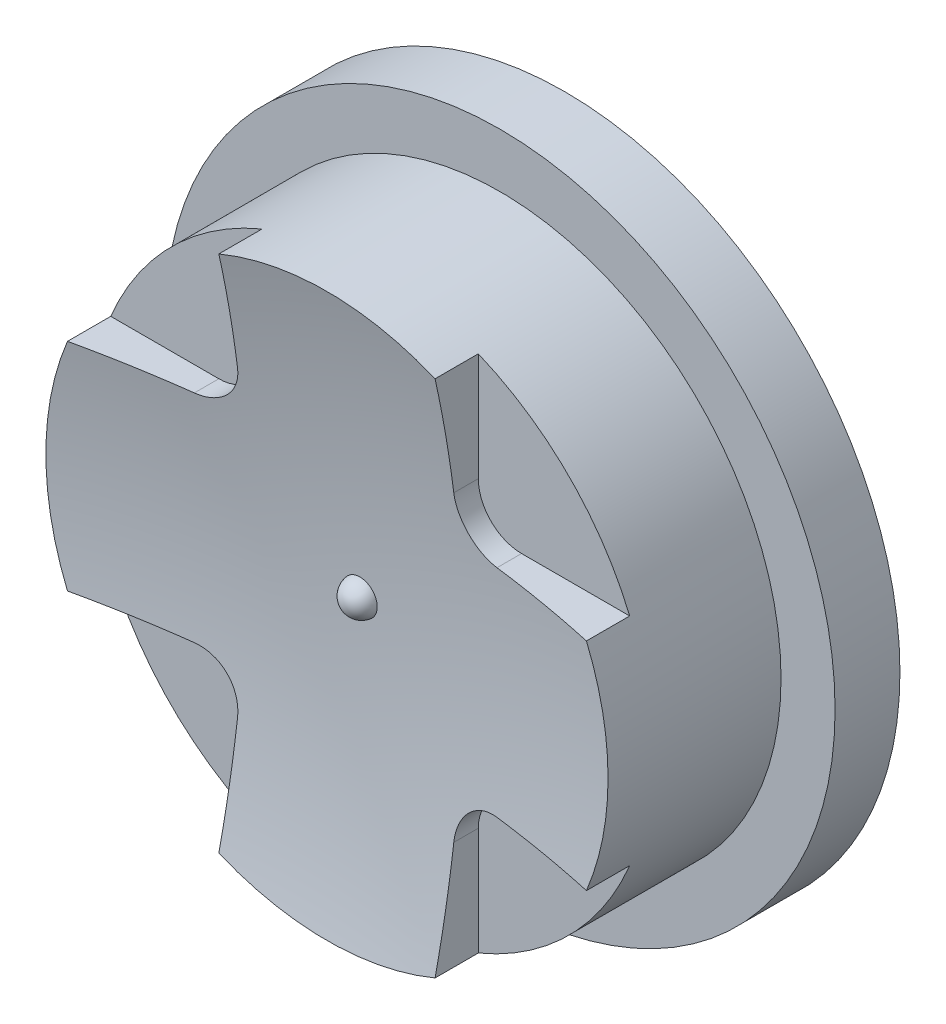
SolidWorks part; units mm, degrees
ref_plane "前视基准面" through (0, 0, 0) normal (0, 0, 1) x (1, 0, 0)
ref_plane "上视基准面" through (0, 0, 0) normal (0, 1, 0) x (1, 0, 0)
ref_plane "右视基准面" through (0, 0, 0) normal (1, 0, 0) x (0, 0, -1)
sketch "草图1" plane through (0, 0, 0) normal (0, 0, 1) x (1, 0, 0)
  circle A0 centre (0, 0) radius 7.75
  dimension "D1" = 15.5
extrude "凸台-拉伸1" add sketch "草图1" along normal blind 1.5
sketch "草图2" plane through (0, 0, 1.5) normal (0, 0, 1) x (1, 0, 0)
  circle A0 centre (0, 0) radius 6.5
  dimension "D1" = 13
extrude "凸台-拉伸2" add sketch "草图2" along normal blind 4
sketch "草图4" plane through (0, 0, 5.5) normal (0, 0, 1) x (1, 0, 0)
  line L0 (-2.5, 7.5) -> (-2.5, 2.5)
  line L1 (-2.5, 2.5) -> (-7.5, 2.5)
  line L2 (-7.5, 2.5) -> (-7.5, -2.5)
  line L3 (-7.5, -2.5) -> (-2.5, -2.5)
  line L4 (-2.5, -2.5) -> (-2.5, -7.5)
  line L5 (-2.5, -7.5) -> (2.5, -7.5)
  line L6 (2.5, -7.5) -> (2.5, -2.5)
  line L7 (2.5, -2.5) -> (7.5, -2.5)
  line L8 (7.5, -2.5) -> (7.5, 2.5)
  line L9 (7.5, 2.5) -> (2.5, 2.5)
  line L10 (2.5, 2.5) -> (2.5, 7.5)
  line L11 (2.5, 7.5) -> (-2.5, 7.5)
  line L12 (-1000, 0) -> (49000, 0) construction
  line L13 (0, -1000) -> (0, 49000) construction
  line L15 (-9.5, 9.5) -> (9.5, 9.5)
  line L16 (-9.5, 9.5) -> (-9.5, -9.5)
  line L17 (-9.5, -9.5) -> (9.5, -9.5)
  line L18 (9.5, 9.5) -> (9.5, -9.5)
  dimension "D1" = 5
  dimension "D2" = 5
  dimension "D3" = 2
extrude "切除-拉伸1" cut sketch "草图4" against normal blind 1
sketch "草图3" plane through (0, 0, 0) normal (0, 1, 0) x (1, 0, 0)
  line L1 (0, -1000) -> (0, 49000) construction
  line L2 (6.5, -5.5) -> (-6.5, -5.5)
  arc A0 (6.5, -5.5) -> (-6.5, -5.5) centre (0, -32.7351) ccw
  dimension "D1" = 28
revolve "切除-旋转2" cut sketch "草图3" angle 360 about L1 region at (2.442, 0, 5.1937)
sketch "草图5" plane through (0, 0, 0) normal (0, 0, -1) x (-1, 0, 0)
  circle A0 centre (0, 0) radius 0.4
  dimension "D1" = 0.8
extrude "凸台-拉伸3" add sketch "草图5" against normal blind 5.1
fillet "圆角1" radius 0.4 1 edges at (-0.4, 0, 5.1)
fillet "圆角2" radius 1 4 edges at (-2.5, 2.5, 4.7296) (2.5, 2.5, 4.7296) (2.5, -2.5, 4.7296) (-2.5, -2.5, 4.7296)
